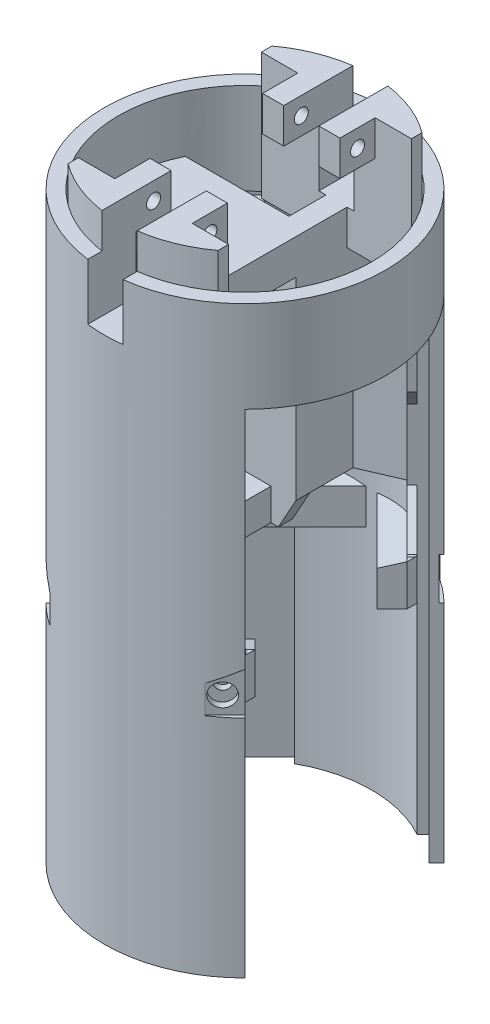
SolidWorks part; units mm, degrees
ref_plane "前视基准面" through (0, 0, 0) normal (0, 0, 1) x (1, 0, 0)
ref_plane "上视基准面" through (0, 0, 0) normal (0, 1, 0) x (1, 0, 0)
ref_plane "右视基准面" through (0, 0, 0) normal (1, 0, 0) x (0, 0, -1)
other "Configuration Table"
sketch "草图1" plane through (0, 0, 0) normal (0, 1, 0) x (1, 0, 0)
  circle A0 centre (0, 0) radius 20
  circle A1 centre (0, 0) radius 18
  dimension "D1" = 40
  dimension "D2" = 36
extrude "凸台-拉伸1" add sketch "草图1" along normal blind 5
sketch "草图2" plane through (0, 0, 0) normal (0, 1, 0) x (1, 0, 0)
  line L0 (0, -1000) -> (0, 49000) construction
  line L2 (-1.5, 17.9374) -> (-1.5, -17.9374)
  line L3 (1.5, 17.9374) -> (1.5, -17.9374)
  arc A0 (-1.5, -17.9374) -> (1.5, -17.9374) centre (0, 0) ccw
  arc A1 (1.5, 17.9374) -> (-1.5, 17.9374) centre (0, 0) ccw
  point P7 (0, 17.9374)
  dimension "D1" = 36
  dimension "D2" = 3
  dimension "D3" = 35.8748
extrude "凸台-拉伸2" add sketch "草图2" along normal blind 5
sketch "草图14" plane through (0, 0, 0) normal (0, 1, 0) x (1, 0, 0)
  line L0 (-1000, 0) -> (49000, 0) construction
  line L1 (0, -1000) -> (0, 49000) construction
  line L2 (-12.4499, 13) -> (12.4499, 13)
  line L3 (-1000, 18) -> (49000, 18) construction
  line L4 (-12.4499, -13) -> (12.4499, -13)
  arc A0 (-12.4499, -13) -> (12.4499, -13) centre (0, 0) ccw
  arc A1 (12.4499, 13) -> (-12.4499, 13) centre (0, 0) ccw
  point P11 (0, 13)
  dimension "D1" = 5
extrude "凸台-拉伸8" add sketch "草图14" along normal up to surface (5 mm away) up to face at (-9.75, 5, 0)
sketch "草图17" plane through (0, 0, 0) normal (0, 1, 0) x (1, 0, 0)
  line L0 (12.4499, 13) -> (2.5, 13)
  line L1 (-1000, 0) -> (49000, 0) construction
  line L12 (-2.5, 13) -> (-12.4499, 13)
  line L26 (-2.5, 17.8255) -> (-2.5, 13)
  line L27 (2.5, 17.8255) -> (2.5, 13)
  line L28 (2.5, -17.8255) -> (2.5, -13)
  line L29 (-2.5, -17.8255) -> (-2.5, -13)
  line L30 (-2.5, -13) -> (-12.4499, -13)
  line L31 (12.4499, -13) -> (2.5, -13)
  arc A0 (-2.5, 17.8255) -> (-12.4499, 13) centre (0, 0) ccw
  arc A1 (12.4499, 13) -> (2.5, 17.8255) centre (0, 0) ccw
  arc A4 (12.4499, -13) -> (2.5, -17.8255) centre (0, 0) cw
  arc A5 (-2.5, -17.8255) -> (-12.4499, -13) centre (0, 0) cw
  dimension "D1" = 4.8255
  dimension "D2" = 5
extrude "凸台-拉伸10" add sketch "草图17" along normal blind 13 from surface starting at face at (8.3625, 5, 0)
sketch "草图25" plane through (0, 0, 0) normal (0, 1, 0) x (1, 0, 0)
  line L1 (1.5, -13) -> (1.5, 13) construction
  line L2 (1.5, -13) -> (1.5, 13) construction
  line L3 (1.5, 7.75) -> (1.5, -7.75)
  line L4 (1.5, -7.75) -> (-16.2462, -7.75)
  line L5 (1.5, 7.75) -> (-16.2462, 7.75)
  arc A0 (-16.2462, 7.75) -> (-16.2462, -7.75) centre (0, 0) ccw
  point P9 (1.5, 0)
  dimension "D1" = 15.5
  dimension "D2" = 17.7462
extrude "凸台-拉伸24" add sketch "草图25" along normal up to surface (5 mm away) from surface up to face at (5.5262, 5, 0) starting at face at (8.3625, 0, 0)
sketch "草图26" plane through (0, 0, 0) normal (0, 1, 0) x (1, 0, 0)
  line L0 (-16.2462, -7.75) -> (1.5, -7.75)
  line L1 (1.5, -13) -> (1.5, 13) construction
  line L2 (1.5, -7.75) -> (1.5, -5.75)
  line L3 (1.5, -5.75) -> (-2.0569, -5.75)
  line L4 (-2.0569, -5.75) -> (-2.0569, 5.75)
  line L5 (-2.0569, 5.75) -> (1.5, 5.75)
  line L6 (1.5, 5.75) -> (1.5, 7.75)
  line L7 (1.5, 7.75) -> (-16.2462, 7.75)
  line L8 (-17.0569, -5.75) -> (-4.0569, -5.75)
  line L9 (-4.0569, -5.75) -> (-4.0569, 5.75)
  line L10 (-4.0569, 5.75) -> (-17.0569, 5.75)
  arc A0 (-16.2462, 7.75) -> (-17.0569, 5.75) centre (0, 0) ccw
  arc A1 (-17.0569, -5.75) -> (-16.2462, -7.75) centre (0, 0) ccw
  dimension "D1" = 2
  dimension "D2" = 2
  dimension "D3" = 2
  dimension "D4" = 13
  dimension "D5" = 11.5
extrude "凸台-拉伸25" add sketch "草图26" against normal blind 32 from surface contours L7 A0 L10 L9 L8 A1 L0 L2 L3 L4 L5 L6 starting at face at (-7.9836, 0, 10.4181)
sketch "草图27" plane through (0, 0, 0) normal (1, 0, 0) x (0, 0, -1)
  line L0 (5.75, 0) -> (-5.75, -32) construction
  line L1 (5.75, -32) -> (-5.75, 0) construction
  line L2 (0, -2.2) -> (0, -29.8) construction
  line L4 (-5.75, -4.5) -> (5.75, -4.5)
  line L5 (-5.75, -4.5) -> (-5.75, -27.5)
  line L6 (-5.75, -27.5) -> (5.75, -27.5)
  line L7 (5.75, -4.5) -> (5.75, -27.5)
  line L8 (-5.75, -4.5) -> (5.75, -27.5) construction
  line L9 (-5.75, -27.5) -> (5.75, -4.5) construction
  circle A0 centre (0, -29.8) radius 1
  circle A1 centre (0, -2.2) radius 1
  point P8 (0, -16)
  point P12 (0, -16)
  point P14 (0, -16)
  dimension "D4" = 2
  dimension "D5" = 2
  dimension "D1" = 27.6
  dimension "D2" = 23
  dimension "D3" = 11.5
extrude "切除-拉伸1" cut sketch "草图27" against normal blind 32
sketch "草图28" plane through (0, 0, 0) normal (0, 0, 1) x (1, 0, 0)
  line L0 (1.5, -32) -> (1.5, -27.5)
  line L1 (1.5, -32) -> (1.5, 0) construction
  line L2 (1.5, -27.5) -> (-1, -32)
  line L3 (1.5, -32) -> (-16.2462, -32) construction
  line L4 (-1, -32) -> (1.5, -32)
  line L5 (-17.0569, -32) -> (-4.0569, -32)
  line L6 (-4.0569, -32) -> (-17.0569, -28.5)
  line L7 (-17.0569, -32) -> (-17.0569, 0) construction
  line L8 (-17.0569, -28.5) -> (-17.0569, -32)
  dimension "D1" = 4.5
  dimension "D2" = 2.5
  dimension "D3" = 3.5
  dimension "D4" = 13
extrude "切除-拉伸2" cut sketch "草图28" against normal through all and the other way blind 32
sketch "草图29" plane through (0, 0, 0) normal (0, 1, 0) x (1, 0, 0)
  line L0 (-17.0569, -5.75) -> (-4.0569, -5.75)
  line L1 (-4.0569, -5.75) -> (-4.0569, -2.75)
  line L2 (-4.0569, 5.75) -> (-4.0569, -5.75) construction
  line L3 (-4.0569, -2.75) -> (-17.7887, -2.75)
  line L4 (-17.0569, 5.75) -> (-4.0569, 5.75)
  line L5 (-4.0569, 5.75) -> (-4.0569, 2.75)
  line L6 (-4.0569, 2.75) -> (-17.7887, 2.75)
  arc A0 (-17.0569, 5.75) -> (-17.7887, 2.75) centre (0, 0) ccw
  arc A1 (-17.7887, -2.75) -> (-17.0569, -5.75) centre (0, 0) ccw
  dimension "D1" = 3
  dimension "D2" = 3
extrude "凸台-拉伸28" add sketch "草图29" along normal blind 1 from surface starting at face at (-3.0569, -4.5, 0)
sketch "草图31" plane through (0, 0, 0) normal (0, 1, 0) x (1, 0, 0)
  line L0 (-17.0569, -5.75) -> (-4.0569, -5.75)
  line L1 (-4.0569, -5.75) -> (-4.0569, -2.75)
  line L2 (-17.0569, 5.75) -> (-4.0569, 5.75)
  line L3 (-4.0569, 5.75) -> (-4.0569, 2.75)
  line L6 (-17.0569, -5.75) -> (-2.0569, -5.75)
  line L7 (-4.0569, -2.75) -> (-17.7887, -2.75)
  line L8 (-4.0569, 2.75) -> (-4.0569, -2.75)
  line L9 (-17.7887, 2.75) -> (-4.0569, 2.75)
  line L10 (-2.0569, 5.75) -> (-17.0569, 5.75)
  line L11 (-2.0569, -5.75) -> (-2.0569, 5.75)
  line L13 (-4.0569, -2.75) -> (-17.7887, -2.75)
  line L15 (-17.7887, 2.75) -> (-4.0569, 2.75)
  arc A2 (-17.7887, -2.75) -> (-17.0569, -5.75) centre (0, 0) ccw
  arc A3 (-17.0569, 5.75) -> (-17.7887, 2.75) centre (0, 0) ccw
  arc A4 (-17.7887, -2.75) -> (-17.0569, -5.75) centre (0, 0) ccw
  arc A5 (-17.0569, 5.75) -> (-17.7887, 2.75) centre (0, 0) ccw
  dimension "D1" = 0
extrude "凸台-拉伸29" add sketch "草图31" against normal blind 1 from surface starting at face at (-3.0569, -27.5, 0)
sketch "草图35" plane through (0, 0, 0) normal (1, 0, 0) x (0, 0, -1)
  line L0 (-8, 18) -> (-13, 13) construction
  line L1 (-13, 18) -> (-8, 18)
  line L2 (-13, 18) -> (-13, 13)
  line L3 (-13, 13) -> (-8, 13)
  line L4 (-8, 18) -> (-8, 13)
  line L5 (13, 18) -> (8, 18)
  line L6 (13, 18) -> (13, 13)
  line L7 (13, 13) -> (8, 13)
  line L8 (8, 18) -> (8, 13)
  line L9 (8, 18) -> (13, 13) construction
  circle A0 centre (10.5, 15.5) radius 1
  circle A1 centre (-10.5, 15.5) radius 1
  dimension "D5" = 2
  dimension "D6" = 2
  dimension "D1" = 5
  dimension "D2" = 5
  dimension "D3" = 5
  dimension "D4" = 5
extrude "凸台-拉伸32" add sketch "草图35" against normal blind 3 from surface starting at face at (-2.5, 11.5, -15.4128)
sketch "草图36" plane through (0, 0, 0) normal (1, 0, 0) x (0, 0, -1)
  line L0 (-13, 13) -> (-13, 18) construction
  line L1 (-13, 18) -> (-8, 18) construction
  line L2 (-8, 18) -> (-8, 13) construction
  line L3 (-8, 13) -> (-13, 13) construction
  line L4 (13, 18) -> (13, 13) construction
  line L5 (13, 13) -> (8, 13) construction
  line L6 (8, 13) -> (8, 18) construction
  line L7 (8, 18) -> (13, 18) construction
  line L8 (-13, 13) -> (-13, 18)
  line L9 (-13, 18) -> (-8, 18)
  line L10 (-8, 18) -> (-8, 13)
  line L11 (-8, 13) -> (-13, 13)
  line L12 (13, 18) -> (13, 13)
  line L13 (13, 13) -> (8, 13)
  line L14 (8, 13) -> (8, 18)
  line L15 (8, 18) -> (13, 18)
  circle A0 centre (-10.5, 15.5) radius 1 construction
  circle A1 centre (-10.5, 15.5) radius 1
  circle A2 centre (10.5, 15.5) radius 1 construction
  circle A3 centre (10.5, 15.5) radius 1
extrude "凸台-拉伸33" add sketch "草图36" along normal blind 3 from surface starting at face at (2.5, 11.5, 15.4128)
sketch "草图37" plane through (0, 0, 0) normal (0, 1, 0) x (1, 0, 0)
  line L0 (2.5, 13) -> (2.5, 17.8255) construction
  line L1 (2.5, -19.8431) -> (2.5, -17.8255)
  line L2 (-2.5, 17.8255) -> (-2.5, 8) construction
  line L3 (-2.5, 19.8431) -> (-2.5, 17.8255)
  line L4 (2.5, 17.8255) -> (2.5, 19.8431)
  line L5 (-2.5, -17.8255) -> (-2.5, -19.8431)
  arc A0 (-2.5, 17.8255) -> (-2.5, -17.8255) centre (0, 0) ccw
  arc A1 (-2.5, 19.8431) -> (-2.5, -19.8431) centre (0, 0) ccw
  arc A2 (2.5, -17.8255) -> (2.5, 17.8255) centre (0, 0) ccw
  arc A3 (2.5, -19.8431) -> (2.5, 19.8431) centre (0, 0) ccw
  dimension "D1" = 40
extrude "凸台-拉伸35" add sketch "草图37" along normal blind 8 from surface starting at face at (5.5262, 5, 0)
sketch "草图38" plane through (0, 0, 0) normal (0, 1, 0) x (1, 0, 0)
  circle A0 centre (0, 0) radius 20
  circle A1 centre (0, 0) radius 18
  dimension "D1" = 40
extrude "凸台-拉伸36" add sketch "草图38" against normal blind 70
sketch "草图39" plane through (0, 0, 0) normal (0, 1, 0) x (1, 0, 0)
  line L0 (-707.1068, -707.1068) -> (34648.2323, 34648.2323) construction
  line L1 (707.1068, -707.1068) -> (-34648.2323, 34648.2323) construction
  line L2 (14.1421, -14.1421) -> (12.7279, -12.7279)
  line L3 (-14.1421, -14.1421) -> (-12.7279, -12.7279)
  line L4 (-12.7279, 12.7279) -> (-14.1421, 14.1421)
  line L5 (14.1421, 14.1421) -> (12.7279, 12.7279)
  arc A0 (14.1421, -14.1421) -> (14.1421, 14.1421) centre (0, 0) ccw
  arc A1 (12.7279, -12.7279) -> (12.7279, 12.7279) centre (0, 0) ccw
  arc A2 (-14.1421, 14.1421) -> (-14.1421, -14.1421) centre (0, 0) ccw
  arc A3 (-12.7279, 12.7279) -> (-12.7279, -12.7279) centre (0, 0) ccw
  dimension "D1" = 40
extrude "切除-拉伸3" cut sketch "草图39" along normal up to surface (70 mm away) from surface up to face at (0, 0, 12.0833) starting at face at (0, -70, 18)
sketch "草图40" plane through (0, 0, 0) normal (0, 1, 0) x (1, 0, 0)
  line L0 (1.5, -7.75) -> (1.5, -17.9374)
  line L1 (-1.5, -17.9374) -> (-1.5, -7.75)
  line L2 (1.5, 7.75) -> (1.5, 17.9374)
  line L3 (-1.5, 7.75) -> (-1.5, 17.9374)
  line L5 (1.5, 13) -> (12.4499, 13)
  line L6 (1.5, 7.75) -> (1.5, 13)
  line L7 (-1.5, 7.75) -> (1.5, 7.75)
  line L8 (-1.5, 13) -> (-1.5, 7.75)
  line L9 (-12.4499, 13) -> (-1.5, 13)
  line L11 (1.5, 7.75) -> (1.5, 13)
  line L12 (-1.5, 7.75) -> (1.5, 7.75)
  line L13 (-1.5, 13) -> (-1.5, 7.75)
  line L15 (-1.5, -13) -> (-12.4499, -13)
  line L16 (-1.5, -7.75) -> (-1.5, -13)
  line L17 (1.5, -7.75) -> (-1.5, -7.75)
  line L18 (1.5, -13) -> (1.5, -7.75)
  line L19 (12.4499, -13) -> (1.5, -13)
  line L21 (-1.5, -7.75) -> (-1.5, -13)
  line L22 (1.5, -7.75) -> (-1.5, -7.75)
  line L23 (1.5, -13) -> (1.5, -7.75)
  arc A1 (12.4499, 13) -> (-12.4499, 13) centre (0, 0) ccw
  arc A2 (1.5, 17.9374) -> (-1.5, 17.9374) centre (0, 0) ccw
  arc A3 (-12.4499, -13) -> (12.4499, -13) centre (0, 0) ccw
  arc A4 (-1.5, -17.9374) -> (1.5, -17.9374) centre (0, 0) ccw
  dimension "D1" = 0
  dimension "D2" = 0
extrude "凸台-拉伸37" add sketch "草图40" against normal up to vertex from surface contours L1 A4 L0 L22 | L2 A2 L3 L12 region at (0, 0, 12.8646) region at (0, 0, -12.8646) up to point (1.5, -27.5, 7.75) starting at face at (-13.4802, 0, 0)
sketch "草图41" plane through (0, 0, 0) normal (0, 1, 0) x (1, 0, 0)
  line L0 (-1000, 0) -> (49000, 0) construction
  line L1 (0, -1000) -> (0, 49000) construction
  line L2 (-707.1068, -707.1068) -> (34648.2323, 34648.2323) construction
  line L3 (707.1068, -707.1068) -> (-34648.2323, 34648.2323) construction
  line L4 (-15.7626, -8.6915) -> (-8.6915, -15.7626)
  line L5 (16.6111, -9.54) -> (9.54, -16.6111)
  line L6 (-16.6111, -9.54) -> (-9.54, -16.6111)
  line L7 (-9.54, -16.6111) -> (-8.6915, -15.7626)
  line L8 (-16.6111, -9.54) -> (-15.7626, -8.6915)
  line L9 (9.54, -16.6111) -> (8.6915, -15.7626)
  line L10 (15.7626, -8.6915) -> (8.6915, -15.7626)
  line L11 (16.6111, -9.54) -> (15.7626, -8.6915)
  line L12 (16.6111, 9.54) -> (15.7626, 8.6915)
  line L13 (15.7626, 8.6915) -> (8.6915, 15.7626)
  line L14 (9.54, 16.6111) -> (8.6915, 15.7626)
  line L15 (16.6111, 9.54) -> (9.54, 16.6111)
  line L16 (-16.6111, 9.54) -> (-9.54, 16.6111)
  line L17 (-9.54, 16.6111) -> (-8.6915, 15.7626)
  line L18 (-15.7626, 8.6915) -> (-8.6915, 15.7626)
  line L19 (-16.6111, 9.54) -> (-15.7626, 8.6915)
  circle A0 centre (0, 0) radius 18 construction
  point P15 (-12.227, -12.227)
  point P21 (-13.0755, -13.0755)
  dimension "D1" = 10
  dimension "D3" = 10
  dimension "D4" = 1.2
extrude "切除-拉伸4" cut sketch "草图41" against normal up to surface (70 mm away) from surface up to face at (0, -70, 16.2175) starting at face at (-13.4802, 0, 0)
sketch "草图42" plane through (0, 0, 0) normal (0, 1, 0) x (1, 0, 0)
  line L0 (-1000, 0) -> (49000, 0) construction
  line L1 (0, -1000) -> (0, 49000) construction
  line L2 (-707.1068, -707.1068) -> (34648.2323, 34648.2323) construction
  line L3 (707.1068, -707.1068) -> (-34648.2323, 34648.2323) construction
  line L4 (-12.227, -12.227) -> (-8.6915, -15.7626)
  line L5 (-11.5199, -11.5199) -> (-6.1077, -16.9321)
  line L6 (-11.5199, -11.5199) -> (-12.227, -12.227)
  line L7 (11.5199, -11.5199) -> (12.227, -12.227)
  line L8 (12.227, -12.227) -> (8.6915, -15.7626)
  line L9 (11.5199, -11.5199) -> (6.1077, -16.9321)
  line L10 (-11.5199, 11.5199) -> (-12.227, 12.227)
  line L11 (-12.227, 12.227) -> (-8.6915, 15.7626)
  line L12 (-11.5199, 11.5199) -> (-6.1077, 16.9321)
  line L13 (11.5199, 11.5199) -> (12.227, 12.227)
  line L14 (12.227, 12.227) -> (8.6915, 15.7626)
  line L15 (11.5199, 11.5199) -> (6.1077, 16.9321)
  arc A0 (-8.6915, -15.7626) -> (-6.1077, -16.9321) centre (0, 0) ccw
  arc A1 (8.6915, -15.7626) -> (6.1077, -16.9321) centre (0, 0) cw
  arc A2 (-8.6915, 15.7626) -> (-6.1077, 16.9321) centre (0, 0) cw
  arc A3 (8.6915, 15.7626) -> (6.1077, 16.9321) centre (0, 0) ccw
  point P15 (-12.227, -12.227)
  point P18 (-11.5199, -11.5199)
  dimension "D1" = 1
extrude "凸台-拉伸39" add sketch "草图42" against normal blind 38 from surface starting at face at (-10.1571, 0, 0)
ref_plane "45度面" through (0, 0, 0) normal (-0.7071, 0, 0.7071) x (0, -1, 0)
sketch "草图44" plane through (0, 0, 0) normal (-0.7071, 0, 0.7071) x (0, -1, 0)
  line L0 (-962, -5) -> (49038, -5) construction
  line L1 (27, -5) -> (17, -5)
  line L3 (27, -5) -> (27, -3) construction
  line L4 (27, -5) -> (32, 0)
  line L5 (38, 0) -> (0, 0) construction
  line L6 (17, -5) -> (17, -3) construction
  line L8 (17, -5) -> (12, 0)
  line L9 (12, 0) -> (32, 0)
  line L10 (0, -20) -> (0, 0) construction
  point P6 (22, -5)
  dimension "D1" = 22
  dimension "D2" = 2
  dimension "D3" = 10
  dimension "D4" = 45
  dimension "D5" = 2
  dimension "D6" = 45
extrude "切除-拉伸5" cut sketch "草图44" against normal up to next from surface starting at face at (9.059, -15.2, -13.9808)
ref_plane "135度面" through (0, 0, 0) normal (-0.7071, 0, -0.7071) x (0, -1, 0)
sketch "草图45" plane through (0, 0, 0) normal (-0.7071, 0, -0.7071) x (0, -1, 0)
  line L0 (70, 5) -> (38, 5) construction
  line L1 (70, 5) -> (38, 5) construction
  line L2 (17, 5) -> (27, 5)
  line L3 (0, -18) -> (0, 0.389) construction
  line L4 (27, 5) -> (27, 3) construction
  line L5 (17, 5) -> (17, 3) construction
  line L7 (27, 5) -> (32, 0)
  line L8 (38, 0) -> (0, 0) construction
  line L9 (32, 0) -> (12, 0)
  line L10 (12, 0) -> (17, 5)
  point P7 (22, 5)
  dimension "D1" = 10
  dimension "D2" = 22
  dimension "D3" = 2
  dimension "D4" = 2
  dimension "D5" = 45
  dimension "D6" = 45
extrude "切除-拉伸6" cut sketch "草图45" against normal up to next from surface starting at face at (9.059, -15.2, 13.9808)
sketch "草图47" plane through (0, 0, 0) normal (-0.7071, 0, 0.7071) x (0, -1, 0)
  line L0 (0, 0) -> (70, 0) construction
  line L1 (0, 0) -> (70, 0) construction
  line L10 (38, 0) -> (38, 4)
  line L12 (38, 0) -> (32, 0)
  line L13 (32, 0) -> (34, 4)
  line L14 (38, 4) -> (34, 4)
  dimension "D1" = 4
  dimension "D2" = 4
extrude "切除-拉伸7" cut sketch "草图47" along normal up to next from offset 19.5
sketch "草图49" plane through (0, 0, 0) normal (-0.7071, 0, 0.7071) x (0, -1, 0)
  line L0 (0, 0) -> (38, 0) construction
  line L1 (0, 0) -> (70, 0) construction
  line L2 (38, 0) -> (38, 7.654) construction
  line L3 (38, 0) -> (38, -4)
  line L4 (38, -4) -> (34, -4)
  line L5 (34, -4) -> (32, 0)
  line L6 (32, -5.5203) -> (32, 2.6114) construction
  line L7 (32, 0) -> (38, 0)
  dimension "D1" = 4
  dimension "D2" = 4
extrude "切除-拉伸8" cut sketch "草图49" against normal up to next from offset 19.5 contours L7 L3 L4 L5 offset against normal yes
sketch "草图50" plane through (0, 0, 0) normal (-0.7071, 0, -0.7071) x (0, -1, 0)
  line L0 (0, 0) -> (38, 0) construction
  line L1 (38, -4) -> (34, -4)
  line L2 (34, -4) -> (32, 0)
  line L3 (38, 0) -> (38, -4)
  line L4 (38, 0) -> (32, 0)
  dimension "D1" = 4
  dimension "D2" = 4
extrude "切除-拉伸9" cut sketch "草图50" along normal up to next from offset 19.5 contours L4 L2 L1 L3
sketch "草图51" plane through (0, 0, 0) normal (-0.7071, 0, -0.7071) x (0, -1, 0)
  line L0 (0, 0) -> (38, 0) construction
  line L1 (38, 0) -> (38, 4)
  line L2 (38, 4) -> (34, 4)
  line L3 (34, 4) -> (31.9993, 0)
  line L4 (31.9993, 0) -> (38, 0)
  dimension "D1" = 4
  dimension "D2" = 4
  dimension "D3" = 6.0007
extrude "切除-拉伸10" cut sketch "草图51" against normal up to next from offset 19.5 offset against normal yes
sketch "草图53" plane through (0, 0, 0) normal (-0.7071, 0, 0.7071) x (0, -1, 0)
  line L0 (0, 0) -> (38, 0) construction
  line L1 (38, 0) -> (38, 4) construction
  circle A0 centre (35.5, 2.25) radius 1.6
  dimension "D1" = 3.2
  dimension "D2" = 2.25
  dimension "D3" = 2.5
extrude "切除-拉伸11" cut sketch "草图53" along normal through all from surface starting at face at (-11.3078, -35, 14.8433)
sketch "草图54" plane through (0, 0, 0) normal (-0.7071, 0, 0.7071) x (0, -1, 0)
  line L0 (38, 0) -> (0, 0) construction
  line L1 (38, 0) -> (38, -4) construction
  circle A0 centre (35.5, -2.225) radius 1.6
  dimension "D3" = 3.2
  dimension "D1" = 2.225
  dimension "D2" = 2.5
extrude "切除-拉伸12" cut sketch "草图54" against normal up to next from surface starting at face at (11.3078, -35, -14.8433)
sketch "草图55" plane through (0, 0, 0) normal (-0.7071, 0, -0.7071) x (0, -1, 0)
  line L0 (38, 0) -> (32, 0) construction
  line L1 (38, 0) -> (38, -4) construction
  circle A0 centre (35.5, -2.25) radius 1.6
  dimension "D1" = 3.2
  dimension "D2" = 2.25
  dimension "D3" = 2.5
extrude "切除-拉伸13" cut sketch "草图55" along normal up to next from surface starting at face at (-11.3078, -35, -14.8433)
sketch "草图56" plane through (0, 0, 0) normal (-0.7071, 0, -0.7071) x (0, -1, 0)
  line L0 (38, 4) -> (38, 0) construction
  line L1 (31.9993, 0) -> (38, 0) construction
  circle A0 centre (35.5, 2.25) radius 1.6
  dimension "D1" = 3.2
  dimension "D2" = 2.5
  dimension "D3" = 2.25
extrude "切除-拉伸14" cut sketch "草图56" against normal up to next from surface contours A0 starting at face at (11.3078, -35, 14.8433)
sketch "草图61" plane through (0, 0, 0) normal (-0.7071, 0, 0.7071) x (0, -1, 0)
  line L0 (33, -13.2916) -> (32.1962, -16.2916)
  line L1 (38, -16.2916) -> (33, -16.2916)
  line L2 (38, -16.2916) -> (38, -13.2916)
  line L3 (38, -13.2916) -> (33, -13.2916)
  line L4 (33, -16.2916) -> (33, -13.2916) construction
  line L5 (32.1962, -16.2916) -> (33, -16.2916)
  dimension "D1" = 3
  dimension "D2" = 5
  dimension "D3" = 15
extrude "凸台-拉伸40" add sketch "草图61" against normal up to next and the other way blind 1 from surface starting at face at (-11.8735, -19, -11.8735)
sketch "草图62" plane through (0, 0, 0) normal (-0.7071, 0, 0.7071) x (0, -1, 0)
  line L0 (33, 13.2916) -> (32.1962, 16.2916)
  line L1 (38, 16.2916) -> (33, 16.2916)
  line L2 (38, 16.2916) -> (38, 13.2916)
  line L3 (38, 13.2916) -> (33, 13.2916)
  line L4 (33, 16.2916) -> (33, 13.2916) construction
  line L5 (38, 16.2916) -> (0, 16.2916) construction
  line L6 (32.1962, 16.2916) -> (33, 16.2916)
  dimension "D1" = 3
  dimension "D2" = 5
  dimension "D3" = 15
extrude "凸台-拉伸41" add sketch "草图62" along normal up to next and the other way blind 1
sketch "草图63" plane through (0, 0, 0) normal (-0.7071, 0, -0.7071) x (0, -1, 0)
  line L0 (38, 16.2916) -> (0, 16.2916) construction
  line L1 (38, 16.2916) -> (33, 16.2916)
  line L2 (38, 16.2916) -> (38, 13.2916)
  line L3 (38, 13.2916) -> (33, 13.2916)
  line L4 (33, 16.2916) -> (33, 13.2916) construction
  line L5 (38, 16.2916) -> (0, 16.2916) construction
  line L6 (33, 13.2916) -> (32.1962, 16.2916)
  line L7 (32.1962, 16.2916) -> (33, 16.2916)
  dimension "D1" = 3
  dimension "D2" = 5
  dimension "D3" = 15
extrude "凸台-拉伸42" add sketch "草图63" against normal up to next and the other way blind 1
sketch "草图64" plane through (0, 0, 0) normal (-0.7071, 0, -0.7071) x (0, -1, 0)
  line L0 (33, -13.2916) -> (32.1962, -16.2916)
  line L1 (38, -16.2916) -> (33, -16.2916)
  line L2 (38, -16.2916) -> (38, -13.2916)
  line L3 (38, -13.2916) -> (33, -13.2916)
  line L4 (33, -16.2916) -> (33, -13.2916) construction
  line L5 (38, -16.2916) -> (0, -16.2916) construction
  line L6 (32.1962, -16.2916) -> (33, -16.2916)
  dimension "D1" = 3
  dimension "D2" = 5
  dimension "D3" = 15
extrude "凸台-拉伸43" add sketch "草图64" along normal up to next and the other way blind 1
sketch "草图67" plane through (0, 0, 0) normal (0, 1, 0) x (1, 0, 0)
  line L0 (7.3833, 13.3937) -> (10.2118, 10.5653)
  line L1 (10.2118, 10.5653) -> (11.3431, 11.6967)
  line L2 (11.3431, 11.6967) -> (8.5147, 14.5251)
  line L3 (8.5147, 14.5251) -> (7.3833, 13.3937)
  line L4 (8.6915, 15.7626) -> (12.227, 12.227) construction
  line L7 (-1000, 0) -> (49000, 0) construction
  line L8 (0, -1000) -> (0, 49000) construction
  line L9 (8.5147, -14.5251) -> (7.3833, -13.3937)
  line L10 (11.3431, -11.6967) -> (8.5147, -14.5251)
  line L11 (10.2118, -10.5653) -> (11.3431, -11.6967)
  line L12 (7.3833, -13.3937) -> (10.2118, -10.5653)
  line L13 (-7.3833, -13.3937) -> (-10.2118, -10.5653)
  line L14 (-10.2118, -10.5653) -> (-11.3431, -11.6967)
  line L15 (-11.3431, -11.6967) -> (-8.5147, -14.5251)
  line L16 (-8.5147, -14.5251) -> (-7.3833, -13.3937)
  line L17 (-8.5147, 14.5251) -> (-7.3833, 13.3937)
  line L18 (-11.3431, 11.6967) -> (-8.5147, 14.5251)
  line L19 (-10.2118, 10.5653) -> (-11.3431, 11.6967)
  line L20 (-7.3833, 13.3937) -> (-10.2118, 10.5653)
  line L23 (12.227, 12.227) -> (11.5199, 11.5199) construction
  dimension "D1" = 1.6
  dimension "D2" = 4
  dimension "D3" = 1
  dimension "D4" = 4.25
extrude "切除-拉伸25" cut sketch "草图67" along normal blind 3.65 from surface starting at face at (9.2858, -38, -12.9081)
sketch "草图71" plane through (0, 0, 0) normal (0, 1, 0) x (1, 0, 0)
  line L0 (12.227, -12.227) -> (12.227, -10.8128)
  line L1 (12.227, -10.8128) -> (11.5199, -11.5199)
  line L2 (11.5199, -11.5199) -> (12.227, -12.227)
  line L3 (11.5199, 11.5199) -> (12.227, 12.227)
  line L4 (12.227, 12.227) -> (12.227, 10.8128)
  line L5 (12.227, 10.8128) -> (11.5199, 11.5199)
  line L6 (-12.227, 12.227) -> (-11.5199, 11.5199)
  line L7 (-11.5199, 11.5199) -> (-12.227, 10.8128)
  line L8 (-12.227, 10.8128) -> (-11.5199, 11.5199) construction
  line L9 (-12.227, 10.8128) -> (-12.227, 12.227)
  line L10 (-12.227, -12.227) -> (-12.227, -10.8128)
  line L11 (-12.227, -10.8128) -> (-11.5199, -11.5199)
  line L12 (-12.227, -10.8128) -> (-11.5199, -11.5199) construction
  line L13 (-12.227, -12.227) -> (-11.5199, -11.5199) construction
  line L14 (-11.5199, -11.5199) -> (-12.227, -12.227)
extrude "凸台-拉伸45" add sketch "草图71" along normal up to vertex from surface up to point (-12.227, -32.1962, 10.8128) starting at face at (-9.2858, -38, 12.9081)
fillet "圆角7" radius 0.2 2 edges at (11.8735, -32.1962, 11.8735) (11.8735, -32.1962, -11.8735)
sketch "草图78" plane through (0, 0, 0) normal (-0.7071, 0, -0.7071) x (0, -1, 0)
  circle A0 centre (35.5, 2.25) radius 1
  dimension "D1" = 2
extrude "切除-拉伸34" cut sketch "草图78" against normal through all
sketch "草图80" plane through (0, 0, 0) normal (-0.7071, 0, 0.7071) x (0, -1, 0)
  circle A0 centre (35.5, 2.25) radius 1
  dimension "D1" = 2
extrude "切除-拉伸36" cut sketch "草图80" along normal through all
sketch "草图81" plane through (0, 0, 0) normal (-0.7071, 0, 0.7071) x (0, -1, 0)
  circle A0 centre (35.5, -2.225) radius 1
  dimension "D1" = 2
extrude "切除-拉伸37" cut sketch "草图81" against normal through all
sketch "草图82" plane through (0, 0, 0) normal (-0.7071, 0, -0.7071) x (0, -1, 0)
  circle A0 centre (35.5, -2.25) radius 1
  dimension "D1" = 2
extrude "切除-拉伸38" cut sketch "草图82" along normal through all
sketch "草图83" plane through (0, 0, 0) normal (-0.7071, 0, 0.7071) x (0, -1, 0)
  line L1 (37.8094, 2.25) -> (36.6547, 4.25)
  line L2 (36.6547, 4.25) -> (34.3453, 4.25)
  line L3 (34.3453, 4.25) -> (33.1906, 2.25)
  line L4 (33.1906, 2.25) -> (34.3453, 0.25)
  line L5 (34.3453, 0.25) -> (36.6547, 0.25)
  line L6 (36.6547, 0.25) -> (37.8094, 2.25)
  circle A0 centre (35.5, 2.25) radius 2 construction
  dimension "D1" = 4
extrude "切除-拉伸39" cut sketch "草图83" against normal blind 1.6 from surface starting at face at (-10.636, -35.5, 12.4038)
sketch "草图84" plane through (0, 0, 0) normal (-0.7071, 0, 0.7071) x (0, -1, 0)
  line L1 (34.3453, -4.225) -> (36.6547, -4.225)
  line L2 (36.6547, -4.225) -> (37.8094, -2.225)
  line L3 (37.8094, -2.225) -> (36.6547, -0.225)
  line L4 (36.6547, -0.225) -> (34.3453, -0.225)
  line L5 (34.3453, -0.225) -> (33.1906, -2.225)
  line L6 (33.1906, -2.225) -> (34.3453, -4.225)
  circle A0 centre (35.5, -2.225) radius 2 construction
  dimension "D1" = 4
extrude "切除-拉伸40" cut sketch "草图84" along normal blind 1.6 from surface starting at face at (10.6537, -35.5, -12.3861)
sketch "草图85" plane through (0, 0, 0) normal (-0.7071, 0, -0.7071) x (0, -1, 0)
  line L1 (37.8094, -2.25) -> (36.6547, -0.25)
  line L2 (36.6547, -0.25) -> (34.3453, -0.25)
  line L3 (34.3453, -0.25) -> (33.1906, -2.25)
  line L4 (33.1906, -2.25) -> (34.3453, -4.25)
  line L5 (34.3453, -4.25) -> (36.6547, -4.25)
  line L6 (36.6547, -4.25) -> (37.8094, -2.25)
  circle A0 centre (35.5, -2.25) radius 2 construction
  point P1 (35.5, -0.25)
  dimension "D1" = 4
extrude "切除-拉伸41" cut sketch "草图85" against normal blind 1.6 from surface starting at face at (-9.2218, -35.5, -13.818)
sketch "草图86" plane through (0, 0, 0) normal (-0.7071, 0, -0.7071) x (0, -1, 0)
  line L1 (33.1906, 2.25) -> (34.3453, 0.25)
  line L2 (34.3453, 0.25) -> (36.6547, 0.25)
  line L3 (36.6547, 0.25) -> (37.8094, 2.25)
  line L4 (37.8094, 2.25) -> (36.6547, 4.25)
  line L5 (36.6547, 4.25) -> (34.3453, 4.25)
  line L6 (34.3453, 4.25) -> (33.1906, 2.25)
  circle A0 centre (35.5, 2.25) radius 2 construction
  dimension "D1" = 4
extrude "切除-拉伸42" cut sketch "草图86" along normal blind 1.6 from surface starting at face at (9.2218, -35.5, 13.818)
sketch "草图87" plane through (0, 0, 0) normal (0, 1, 0) x (1, 0, 0)
  line L3 (-5.5, -13) -> (-12.4499, -13) construction
  line L5 (12.4499, -13) -> (5.5, -13) construction
  line L11 (5.5, 13) -> (12.4499, 13) construction
  line L13 (-12.4499, 13) -> (-5.5, 13) construction
  line L19 (-10.6654, -13) -> (-12.4499, -13)
  line L21 (12.4499, -13) -> (10.6654, -13)
  line L27 (10.6654, 13) -> (12.4499, 13)
  line L29 (-12.4499, 13) -> (-10.6654, 13)
  line L32 (10.6654, 13) -> (10.6654, 14.5)
  line L33 (10.6654, -13) -> (10.6654, -14.5)
  line L34 (-10.6654, -13) -> (-10.6654, -14.5)
  line L35 (-10.6654, 14.5) -> (-10.6654, 13)
  arc A0 (-12.4499, -13) -> (-2.5, -17.8255) centre (0, 0) ccw construction
  arc A1 (2.5, -17.8255) -> (12.4499, -13) centre (0, 0) ccw construction
  arc A2 (12.4499, 13) -> (2.5, 17.8255) centre (0, 0) ccw construction
  arc A3 (-2.5, 17.8255) -> (-12.4499, 13) centre (0, 0) ccw construction
  arc A4 (-12.4499, -13) -> (-10.6654, -14.5) centre (0, 0) ccw
  arc A5 (10.6654, -14.5) -> (12.4499, -13) centre (0, 0) ccw
  arc A6 (12.4499, 13) -> (10.6654, 14.5) centre (0, 0) ccw
  arc A7 (-10.6654, 14.5) -> (-12.4499, 13) centre (0, 0) ccw
  dimension "D1" = 1.5
  dimension "D2" = 1.5
  dimension "D3" = 1.5
extrude "切除-拉伸43" cut sketch "草图87" against normal up to surface from surface up to face at (4.7952, 0, -15.2553) starting at face at (-5.7659, 18, -12.1217)
sketch "草图88" plane through (0, 0, 0) normal (0, 1, 0) x (1, 0, 0)
  line L0 (1.5, 17.9374) -> (1.5, 14.9374) construction
  line L1 (1.5, 17.9374) -> (1.5, 7.75) construction
  line L2 (1.5, 14.9374) -> (6.1077, 16.9321)
  line L3 (-1.5, 14.9374) -> (-6.1077, 16.9321)
  line L4 (-1.5, 17.9374) -> (-1.5, 7.75) construction
  line L5 (-1.5, 14.9374) -> (-1.5, 17.9374) construction
  line L6 (1.5, -17.9374) -> (1.5, -14.9374) construction
  line L7 (1.5, -17.9374) -> (1.5, -7.75) construction
  line L8 (-1.5, -14.9374) -> (-6.1077, -16.9321)
  line L9 (-1.5, -14.9374) -> (-1.5, -17.9374) construction
  line L10 (-1.5, -7.75) -> (-1.5, -17.9374) construction
  line L11 (1.5, -14.9374) -> (6.1077, -16.9321)
  line L12 (6.8682, -16.1716) -> (1.5, -13.8477)
  line L13 (11.6613, -11.3785) -> (6.1077, -16.9321) construction
  line L14 (1.5, -13.8477) -> (1.5, -14.9374)
  line L15 (6.8682, -16.1716) -> (6.1077, -16.9321)
  line L16 (1.5, -13.8477) -> (1.5, -14.9374)
  line L17 (-1.5, -13.8477) -> (-6.8682, -16.1716)
  line L18 (-11.5199, -11.5199) -> (-6.1077, -16.9321) construction
  line L19 (-6.8682, -16.1716) -> (-6.1077, -16.9321)
  line L20 (-1.5, -13.8477) -> (-1.5, -14.9374)
  line L21 (6.8682, 16.1716) -> (1.5, 13.8477)
  line L22 (11.6613, 11.3785) -> (6.1077, 16.9321) construction
  line L23 (6.8682, 16.1716) -> (6.1077, 16.9321)
  line L24 (1.5, 14.9374) -> (1.5, 13.8477)
  line L25 (-1.5, 13.8477) -> (-6.941, 16.2031)
  line L26 (-1.5, 14.9374) -> (-1.5, 13.8477)
  line L27 (-6.1077, 16.9321) -> (-6.8682, 16.1716)
  line L28 (-11.5199, 11.5199) -> (-6.1077, 16.9321) construction
  arc A0 (0.8157, -17.9815) -> (6.1077, -16.9321) centre (0, 0) ccw construction
  arc A1 (-6.1077, -16.9321) -> (-0.8157, -17.9815) centre (0, 0) ccw construction
  arc A2 (6.1077, 16.9321) -> (0.8157, 17.9815) centre (0, 0) ccw construction
  arc A3 (-0.8157, 17.9815) -> (-6.1077, 16.9321) centre (0, 0) ccw construction
  arc A4 (0.8157, -17.9815) -> (6.1077, -16.9321) centre (0, 0) ccw construction
  arc A5 (-6.1077, -16.9321) -> (-0.8157, -17.9815) centre (0, 0) ccw construction
  arc A6 (6.1077, 16.9321) -> (0.8157, 17.9815) centre (0, 0) ccw construction
  arc A7 (-0.8157, 17.9815) -> (-6.1077, 16.9321) centre (0, 0) ccw construction
  dimension "D7" = 1
  dimension "D1" = 3
  dimension "D2" = 3
  dimension "D3" = 3
  dimension "D4" = 3
  dimension "D5" = 1
  dimension "D6" = 1
  dimension "D8" = 1
extrude "凸台-拉伸46" add sketch "草图88" along normal blind 15 from surface contours L2 L24 L21 L23 | L3 L27 L25 L26 | L15 L12 L14 L11 | L20 L17 L19 L8 region at (3.9988, 0, -15.4604) region at (-3.9988, 0, -15.4604) region at (-3.9988, 0, 15.4604) region at (3.9988, 0, 15.4604) starting at face at (0, -27.5, -12.8593)
